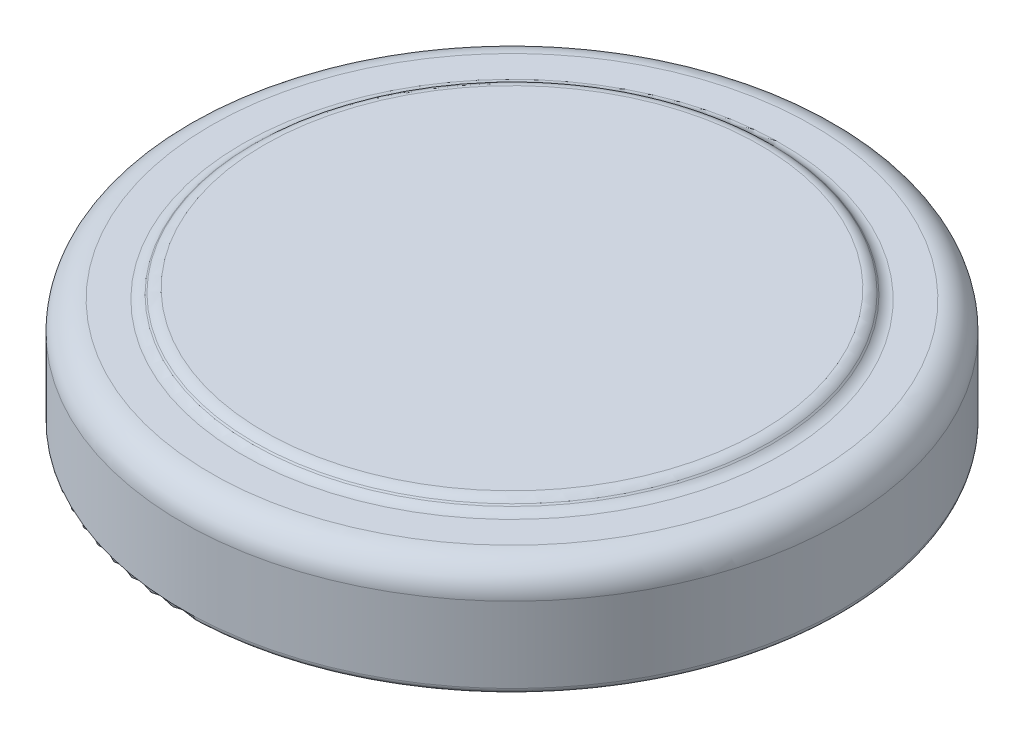
SolidWorks part; units mm, degrees
ref_plane "Front Plane" through (0, 0, 0) normal (0, 0, 1) x (1, 0, 0)
ref_plane "Top Plane" through (0, 0, 0) normal (0, 1, 0) x (1, 0, 0)
ref_plane "Right Plane" through (0, 0, 0) normal (1, 0, 0) x (0, 0, -1)
sketch "Sketch1" plane through (0, 0, 0) normal (0, 0, 1) x (1, 0, 0)
  line L0 (0, 0) -> (-5.7, 0)
  line L1 (-5.8, 0.1) -> (-5.8, 1.43)
  line L2 (-4.3664, 2.1) -> (0, 2.1)
  line L3 (0, 2.1) -> (0, 0)
  line L4 (-4.5432, 2.0268) -> (-4.5668, 2.0032)
  line L7 (-5.3, 1.93) -> (-4.7436, 1.93)
  arc A0 (-5.8, 1.43) -> (-5.3, 1.93) centre (-5.3, 1.43) cw
  arc A1 (-4.3664, 2.1) -> (-4.5432, 2.0268) centre (-4.3664, 1.85) ccw
  arc A2 (-4.7436, 1.93) -> (-4.5668, 2.0032) centre (-4.7436, 2.18) ccw
  arc A3 (-5.7, 0) -> (-5.8, 0.1) centre (-5.7, 0.1) cw
  point P9 (-5.8, 1.93)
  point P14 (-4.47, 2.1)
  point P17 (-5.8, 0)
  point P18 (-4.64, 1.93)
  dimension "D6" = 0.5
  dimension "D7" = 0.25
  dimension "D8" = 0.1
  dimension "D1" = 5.8
  dimension "D2" = 2.1
  dimension "D3" = 4.64
  dimension "D4" = 1.93
  dimension "D5" = 45
revolve "Revolve1" add sketch "Sketch1" angle 360 about L3
sketch "Sketch2" plane through (0, 0, 0) normal (0, -1, 0) x (1, 0, 0)
  line L0 (0.25, 0.25) -> (2, 0.25)
  line L1 (-0.25, 2) -> (0.25, 2)
  line L2 (-0.25, 2) -> (-0.25, 0.25)
  line L3 (-0.25, -2) -> (0.25, -2)
  line L4 (0.25, 2) -> (0.25, 0.25)
  line L5 (-2, 0.25) -> (-0.25, 0.25)
  line L6 (-2, 0.25) -> (-2, -0.25)
  line L7 (-2, -0.25) -> (-0.25, -0.25)
  line L8 (2, 0.25) -> (2, -0.25)
  line L9 (0.25, -0.25) -> (2, -0.25)
  line L10 (0.25, -0.25) -> (0.25, -2)
  line L11 (-0.25, -0.25) -> (-0.25, -2)
  circle A0 centre (0, 0) radius 4 construction
  text T0 "                                SR55" font "Century Gothic" height 1
  dimension "D1" = 8
  dimension "D2" = 0.5
  dimension "D3" = 0.5
  dimension "D4" = 0.25
  dimension "D5" = 0.25
  dimension "D6" = 4
  dimension "D7" = 2
  dimension "D8" = 4
  dimension "D9" = 2
wrap "Wrap1" sketch "Sketch2" wrap type scribe source sketch "Sketch2" face at (-5.7, 0, 0)
